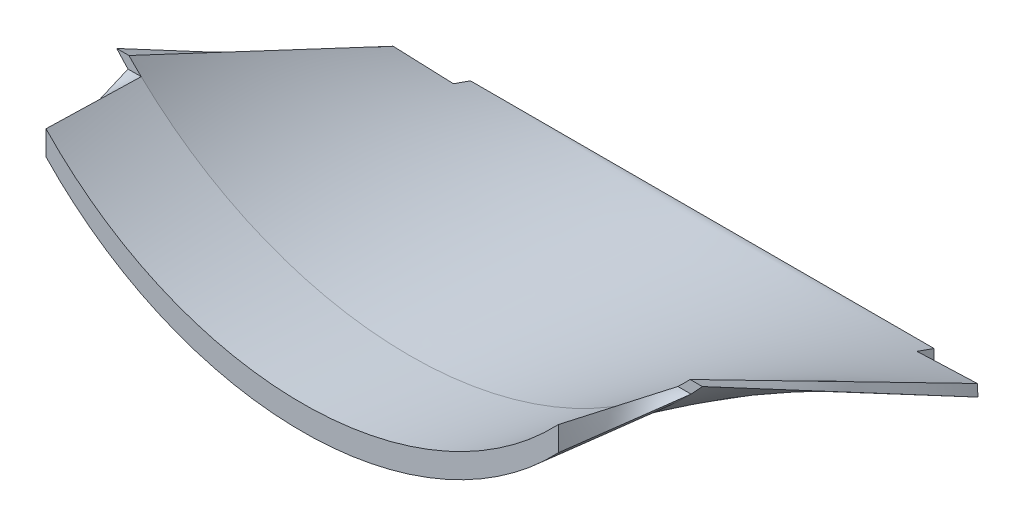
SolidWorks part; units mm, degrees
ref_plane "Plan de face" through (0, 0, 0) normal (0, 0, 1) x (1, 0, 0)
ref_plane "Plan de dessus" through (0, 0, 0) normal (0, 1, 0) x (1, 0, 0)
ref_plane "Plan de droite" through (0, 0, 0) normal (1, 0, 0) x (0, 0, -1)
sketch "Esquisse1" plane through (0, 0, 0) normal (0, 0, 1) x (1, 0, 0)
  line L1 (0, 0) -> (240, 0)
  line L2 (0, 0) -> (0, 5)
  line L3 (0, 5) -> (240, 5)
  line L4 (240, 0) -> (240, 5)
  dimension "D1" = 5
  dimension "D2" = 240
ref_plane "Plan1" through (0, 0, 164) normal (0, 0, 1) x (1, 0, 0)
sketch "Esquisse3" plane through (0, 0, 164) normal (0, 0, 1) x (1, 0, 0)
  line L0 (0, 0) -> (120, 0) construction
  line L1 (120, 0) -> (120, 10) construction
  line L2 (120, 10) -> (15, 10) construction
  line L3 (15, 10) -> (15, 55) construction
  line L4 (225, 10) -> (225, 55) construction
  line L5 (15, 55) -> (15, 65)
  line L6 (225, 55) -> (225, 65)
  arc A0 (15, 55) -> (225, 55) centre (120, 155) ccw
  arc A1 (15, 65) -> (225, 65) centre (120, 165) ccw
  dimension "D1" = 120
  dimension "D2" = 10
  dimension "D3" = 45
  dimension "D4" = 105
  dimension "D5" = 2
ref_plane "Plan2" through (0, 0, 120) normal (0, 0, 1) x (1, 0, 0)
sketch "Esquisse4" plane through (0, 0, 120) normal (0, 0, 1) x (1, 0, 0)
  line L0 (0, 0) -> (120, 0) construction
  line L1 (120, 0) -> (120, 10) construction
  line L2 (120, 10) -> (120, 64) construction
  line L3 (120, 64) -> (0, 64) construction
  line L4 (120, 64) -> (240, 64) construction
  line L5 (0, 64) -> (5, 64)
  line L6 (240, 64) -> (235, 64)
  line L7 (120, 10) -> (120, 15) construction
  arc A0 (0, 64) -> (240, 64) centre (120, 170.3333) ccw
  arc A1 (5, 64) -> (235, 64) centre (120, 174.449) ccw
  point P10 (120, 64)
  dimension "D1" = 120
  dimension "D2" = 10
  dimension "D3" = 54
  dimension "D4" = 2
  dimension "D5" = 5
loft "Lissage1" add profiles "Esquisse1", "Esquisse4" connector at (0, 0, 0) connector at (0, 64, 120)
sketch "Esquisse5" plane through (0, 0, 120) normal (0, 0, 1) x (1, 0, 0)
  line L0 (0, 64) -> (0, 59) construction
  line L1 (0, 59) -> (4.6238, 59) construction
  line L2 (4.6238, 59) -> (10.0204, 59)
  line L3 (120, 10) -> (120, 27.7012) construction
  line L4 (235.3762, 59) -> (229.9796, 59)
  arc A0 (0, 64) -> (240, 64) centre (120, 170.3333) ccw construction
  arc A1 (5, 64) -> (235, 64) centre (120, 174.449) ccw construction
  arc A2 (4.6238, 59) -> (235.3762, 59) centre (120, 170.3333) ccw
  arc A3 (10.0204, 59) -> (229.9796, 59) centre (120, 174.449) ccw
  dimension "D1" = 5
loft "Lissage2" add profiles "Esquisse5", "Esquisse3" connector at (4.6238, 59, 120) connector at (15, 55, 164)
sketch "Esquisse6" plane through (0, 0, 0) normal (0, 1, 0) x (1, 0, 0)
  line L1 (240, 0) -> (215, 0) construction
  line L2 (240, 0) -> (240, -7) construction
  line L3 (240, -7) -> (215, -7)
  line L4 (215, 0) -> (215, -7)
  line L5 (0, 0) -> (25, 0) construction
  line L6 (0, 0) -> (0, -7) construction
  line L7 (0, -7) -> (25, -7)
  line L8 (25, 0) -> (25, -7)
  line L9 (25, -7) -> (-11.7845, -7)
  line L10 (25, -7) -> (25, 17.3453)
  line L11 (25, 17.3453) -> (-11.7845, 17.3453)
  line L12 (-11.7845, -7) -> (-11.7845, 17.3453)
  line L13 (215, -7) -> (256.4712, -7)
  line L14 (215, -7) -> (215, 16.0573)
  line L15 (215, 16.0573) -> (256.4712, 16.0573)
  line L16 (256.4712, -7) -> (256.4712, 16.0573)
  dimension "D1" = 7
  dimension "D2" = 25
extrude "Enlèv. mat.-Extru.6" cut sketch "Esquisse6" along normal through all contours L13 L16 L15 L14 L4 L3 | L9 L12 L11 L10 region at (235.7356, 0, -4.5286)
